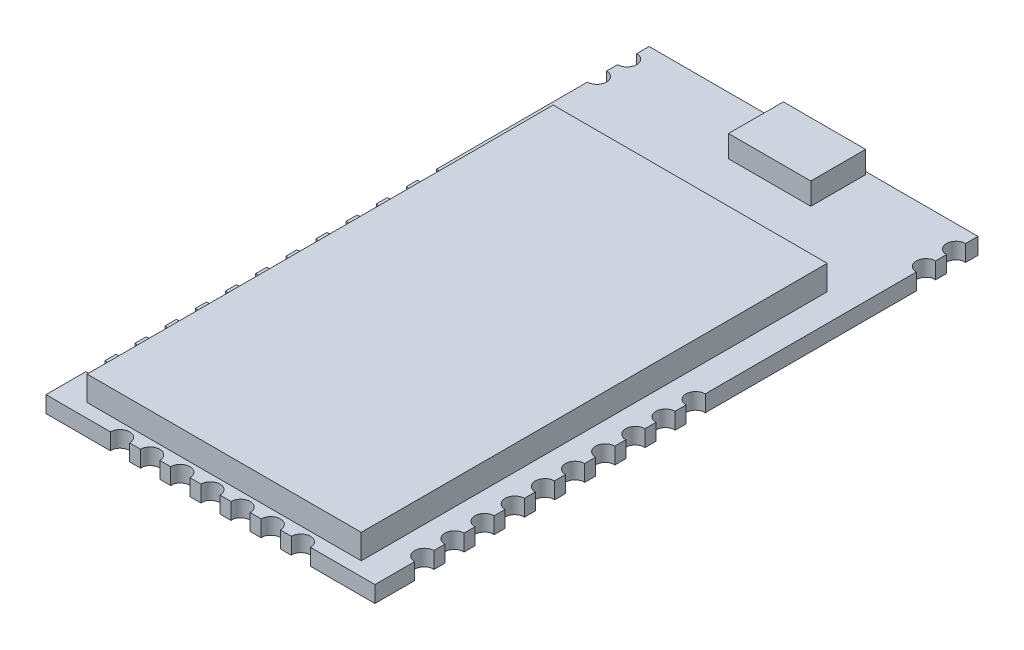
SolidWorks part; units mm, degrees
ref_plane "Front Plane" through (0, 0, 0) normal (0, 0, 1) x (1, 0, 0)
ref_plane "Top Plane" through (0, 0, 0) normal (0, 1, 0) x (1, 0, 0)
ref_plane "Right Plane" through (0, 0, 0) normal (1, 0, 0) x (0, 0, -1)
sketch "Sketch1" plane through (0, 0, 0) normal (0, 1, 0) x (1, 0, 0)
  line L0 (-6, -11) -> (-6, 11)
  line L1 (-6, 11) -> (6, 11)
  line L2 (6, 11) -> (6, -11)
  line L3 (6, -11) -> (-6, -11)
  line L4 (6, -11) -> (-6, 11) construction
  dimension "D1" = 22
  dimension "D2" = 12
extrude "Boss-Extrude1" add sketch "Sketch1" along normal blind 0.6
sketch "Sketch2" plane through (0, 0, 0) normal (0, 1, 0) x (1, 0, 0)
  line L4 (-6, -11) -> (6, -11)
  line L5 (6, -11) -> (6, 11)
  line L6 (6, 11) -> (-6, 11)
  line L7 (-6, 11) -> (-6, -11)
  line L8 (-6, -11) -> (6, -11) construction
  line L9 (6, -11) -> (6, 11) construction
  line L10 (6, 11) -> (-6, 11) construction
  line L11 (-6, 11) -> (-6, -11) construction
  circle A0 centre (-6, -9.2) radius 0.35
  circle A1 centre (-6, -8.1) radius 0.35
  circle A2 centre (-6, -7) radius 0.35
  circle A3 centre (-6, -5.9) radius 0.35
  circle A4 centre (-6, -4.8) radius 0.35
  circle A5 centre (-6, -3.7) radius 0.35
  circle A6 centre (-6, -2.6) radius 0.35
  circle A7 centre (-6, -1.5) radius 0.35
  circle A8 centre (-6, -0.4) radius 0.35
  circle A9 centre (-6, 0.7) radius 0.35
  circle A10 centre (-6, 1.8) radius 0.35
  circle A11 centre (-6, 2.9) radius 0.35
  dimension "D2" = 0.7
  dimension "D3" = 1.8
  dimension "D1" = 0
  dimension "D4" = 12
extrude "Pins left" cut sketch "Sketch2" along normal through all
sketch "Sketch3" plane through (0, 0.6, 0) normal (0, 1, 0) x (1, 0, 0)
  line L0 (-6, -11) -> (6, -11) construction
  line L1 (-6, -9.55) -> (-6, -11) construction
  circle A0 centre (-3.3, -11) radius 0.35
  circle A1 centre (-2.2, -11) radius 0.35
  circle A2 centre (-1.1, -11) radius 0.35
  circle A3 centre (0, -11) radius 0.35
  circle A4 centre (1.1, -11) radius 0.35
  circle A5 centre (2.2, -11) radius 0.35
  circle A6 centre (3.3, -11) radius 0.35
  dimension "D1" = 0.7
  dimension "D2" = 2.7
  dimension "D3" = 7
extrude "Cut-Extrude4" cut sketch "Sketch3" against normal blind 0.6
sketch "Sketch4" plane through (0, 0.6, 0) normal (0, 1, 0) x (1, 0, 0)
  line L0 (6, -11) -> (6, 11) construction
  line L1 (3.65, -11) -> (6, -11) construction
  circle A0 centre (6, -9.2) radius 0.35
  circle A1 centre (6, -8.1) radius 0.35
  circle A2 centre (6, -7) radius 0.35
  circle A3 centre (6, -5.9) radius 0.35
  circle A4 centre (6, -4.8) radius 0.35
  circle A5 centre (6, -3.7) radius 0.35
  circle A6 centre (6, -2.6) radius 0.35
  circle A7 centre (6, -1.5) radius 0.35
  circle A8 centre (6, -0.4) radius 0.35
  circle A9 centre (6, 0.7) radius 0.35
  dimension "D1" = 0.7
  dimension "D2" = 1.8
  dimension "D3" = 10
extrude "Cut-Extrude5" cut sketch "Sketch4" against normal blind 0.6
sketch "Sketch9" plane through (0, 0, 0) normal (0, -1, 0) x (1, 0, 0)
  line L0 (-6, -11) -> (-6, -3.25) construction
  line L1 (0, -11.597) -> (0, 0) construction
  circle A0 centre (-6, -9.1) radius 0.35
  circle A1 centre (-6, -10.2) radius 0.35
  circle A2 centre (6, -9.1) radius 0.35
  circle A3 centre (6, -10.2) radius 0.35
  dimension "D1" = 0.7
  dimension "D2" = 20.1
  dimension "D3" = 1.1
extrude "Cut-Extrude9" cut sketch "Sketch9" against normal blind 0.6
sketch "Sketch5" plane through (0, 0.6, 0) normal (0, 1, 0) x (1, 0, 0)
  line L0 (6, 1.05) -> (6, 8.75) construction
  line L1 (-5, 6.5) -> (5, 6.5)
  line L2 (-5, 6.5) -> (-5, -10.5)
  line L3 (-5, -10.5) -> (5, -10.5)
  line L4 (5, 6.5) -> (5, -10.5)
  line L5 (-5, 6.5) -> (5, -10.5) construction
  line L6 (-5, -10.5) -> (5, 6.5) construction
  line L7 (-6, -11) -> (-3.65, -11) construction
  line L13 (-1, 10.9) -> (2, 10.9)
  line L14 (-1, 10.9) -> (-1, 8.9)
  line L15 (-1, 8.9) -> (2, 8.9)
  line L16 (2, 10.9) -> (2, 8.9)
  line L17 (-1, 10.9) -> (2, 8.9) construction
  line L18 (-1, 8.9) -> (2, 10.9) construction
  line L19 (6, 11) -> (-6, 11) construction
  point P0 (0, -2)
  point P5 (0.5, 9.9)
  point P7 (0, -1.6618)
  point P16 (0, 0)
  point P17 (0, 0)
  point P18 (1.05, 9.1598)
  point P19 (0, 0)
  point P24 (-1, 9.9)
  dimension "D1" = 10
  dimension "D2" = 17
  dimension "D3" = 5.5
  dimension "D4" = 1.1
  dimension "D5" = 3
  dimension "D6" = 2
  dimension "D7" = 0.5
extrude "Boss-Extrude2" add sketch "Sketch5" along normal blind 0.9 contours L4 L3 L2 L1
extrude "Boss-Extrude3" add sketch "Sketch5<3>" along normal blind 0.8 contours L16 L15 L14 L13
sketch "Sketch5<3>" plane through (0, 0.6, 0) normal (0, 1, 0) x (1, 0, 0) same geometry as "Sketch5"
sketch "Sketch7" plane through (0, 0, 0) normal (0, -1, 0) x (1, 0, 0)
  line L0 (2.55, 12) -> (2.55, 10)
  line L1 (3.65, 12) -> (2.95, 12)
  line L2 (3.65, 12) -> (3.65, 10)
  line L3 (3.65, 10) -> (2.95, 10)
  line L4 (2.95, 12) -> (2.95, 10)
  line L5 (3.65, 12) -> (2.95, 10) construction
  line L6 (3.65, 10) -> (2.95, 12) construction
  line L7 (2.55, 10) -> (1.85, 10)
  line L8 (1.85, 12) -> (1.85, 10)
  line L9 (2.55, 12) -> (1.85, 12)
  line L10 (1.45, 12) -> (1.45, 10)
  line L11 (1.45, 10) -> (0.75, 10)
  line L12 (0.75, 12) -> (0.75, 10)
  line L13 (1.45, 12) -> (0.75, 12)
  line L14 (0.35, 12) -> (0.35, 10)
  line L15 (0.35, 10) -> (-0.35, 10)
  line L16 (-0.35, 12) -> (-0.35, 10)
  line L17 (0.35, 12) -> (-0.35, 12)
  line L18 (-0.75, 12) -> (-0.75, 10)
  line L19 (-0.75, 10) -> (-1.45, 10)
  line L20 (-1.45, 12) -> (-1.45, 10)
  line L21 (-0.75, 12) -> (-1.45, 12)
  line L22 (-1.85, 12) -> (-1.85, 10)
  line L23 (-1.85, 10) -> (-2.55, 10)
  line L24 (-2.55, 12) -> (-2.55, 10)
  line L25 (-1.85, 12) -> (-2.55, 12)
  line L26 (-2.95, 12) -> (-2.95, 10)
  line L27 (-2.95, 10) -> (-3.65, 10)
  line L28 (-3.65, 12) -> (-3.65, 10)
  line L29 (-2.95, 12) -> (-3.65, 12)
  arc A0 (2.95, 11) -> (3.65, 11) centre (3.3, 11) ccw construction
  point P0 (3.3, 11)
  dimension "D1" = 1
  dimension "D2" = 7
extrude "Cut-Extrude7" cut sketch "Sketch7" against normal blind 0.01
sketch "Sketch8" plane through (0, 0, 0) normal (0, -1, 0) x (1, 0, 0)
  line L0 (-5, 7.75) -> (-7, 7.75)
  line L1 (-5, 9.55) -> (-7, 9.55)
  line L2 (-5, 9.55) -> (-5, 8.85)
  line L3 (-5, 8.85) -> (-7, 8.85)
  line L4 (-7, 9.55) -> (-7, 8.85)
  line L5 (-5, 9.55) -> (-7, 8.85) construction
  line L6 (-5, 8.85) -> (-7, 9.55) construction
  line L7 (-7, 8.45) -> (-7, 7.75)
  line L8 (-5, 8.45) -> (-7, 8.45)
  line L9 (-5, 8.45) -> (-5, 7.75)
  line L10 (-5, 6.65) -> (-7, 6.65)
  line L11 (-7, 7.35) -> (-7, 6.65)
  line L12 (-5, 7.35) -> (-7, 7.35)
  line L13 (-5, 7.35) -> (-5, 6.65)
  line L14 (-5, 5.55) -> (-7, 5.55)
  line L15 (-7, 6.25) -> (-7, 5.55)
  line L16 (-5, 6.25) -> (-7, 6.25)
  line L17 (-5, 6.25) -> (-5, 5.55)
  line L18 (-5, 4.45) -> (-7, 4.45)
  line L19 (-7, 5.15) -> (-7, 4.45)
  line L20 (-5, 5.15) -> (-7, 5.15)
  line L21 (-5, 5.15) -> (-5, 4.45)
  line L22 (-5, 3.35) -> (-7, 3.35)
  line L23 (-7, 4.05) -> (-7, 3.35)
  line L24 (-5, 4.05) -> (-7, 4.05)
  line L25 (-5, 4.05) -> (-5, 3.35)
  line L26 (-5, 2.25) -> (-7, 2.25)
  line L27 (-7, 2.95) -> (-7, 2.25)
  line L28 (-5, 2.95) -> (-7, 2.95)
  line L29 (-5, 2.95) -> (-5, 2.25)
  line L30 (-5, 1.15) -> (-7, 1.15)
  line L31 (-7, 1.85) -> (-7, 1.15)
  line L32 (-5, 1.85) -> (-7, 1.85)
  line L33 (-5, 1.85) -> (-5, 1.15)
  line L34 (-5, 0.05) -> (-7, 0.05)
  line L35 (-7, 0.75) -> (-7, 0.05)
  line L36 (-5, 0.75) -> (-7, 0.75)
  line L37 (-5, 0.75) -> (-5, 0.05)
  line L38 (-5, -1.05) -> (-7, -1.05)
  line L39 (-7, -0.35) -> (-7, -1.05)
  line L40 (-5, -0.35) -> (-7, -0.35)
  line L41 (-5, -0.35) -> (-5, -1.05)
  line L42 (-5, -2.15) -> (-7, -2.15)
  line L43 (-7, -1.45) -> (-7, -2.15)
  line L44 (-5, -1.45) -> (-7, -1.45)
  line L45 (-5, -1.45) -> (-5, -2.15)
  line L46 (-5, -3.25) -> (-7, -3.25)
  line L47 (-7, -2.55) -> (-7, -3.25)
  line L48 (-5, -2.55) -> (-7, -2.55)
  line L49 (-5, -2.55) -> (-5, -3.25)
  arc A0 (-6, 8.85) -> (-6, 9.55) centre (-6, 9.2) ccw construction
  point P0 (-6, 9.2)
  dimension "D1" = 1
  dimension "D2" = 12
extrude "Cut-Extrude8" cut sketch "Sketch8" against normal blind 0.01
sketch "Sketch10" plane through (0, 0, 0) normal (0, -1, 0) x (1, 0, 0)
  line L1 (4.65, 8.85) -> (6.65, 8.85)
  line L2 (4.65, 8.85) -> (4.65, 9.55)
  line L3 (4.65, 9.55) -> (6.65, 9.55)
  line L4 (6.65, 8.85) -> (6.65, 9.55)
  line L5 (4.65, 8.85) -> (6.65, 9.55) construction
  line L6 (4.65, 9.55) -> (6.65, 8.85) construction
  line L7 (4.65, 7.75) -> (4.65, 8.45)
  line L8 (4.65, 7.75) -> (6.65, 7.75)
  line L9 (6.65, 7.75) -> (6.65, 8.45)
  line L10 (4.65, 8.45) -> (6.65, 8.45)
  line L11 (4.65, 6.65) -> (4.65, 7.35)
  line L12 (4.65, 6.65) -> (6.65, 6.65)
  line L13 (6.65, 6.65) -> (6.65, 7.35)
  line L14 (4.65, 7.35) -> (6.65, 7.35)
  line L15 (4.65, 5.55) -> (4.65, 6.25)
  line L16 (4.65, 5.55) -> (6.65, 5.55)
  line L17 (6.65, 5.55) -> (6.65, 6.25)
  line L18 (4.65, 6.25) -> (6.65, 6.25)
  line L19 (4.65, 4.45) -> (4.65, 5.15)
  line L20 (4.65, 4.45) -> (6.65, 4.45)
  line L21 (6.65, 4.45) -> (6.65, 5.15)
  line L22 (4.65, 5.15) -> (6.65, 5.15)
  line L23 (4.65, 3.35) -> (4.65, 4.05)
  line L24 (4.65, 3.35) -> (6.65, 3.35)
  line L25 (6.65, 3.35) -> (6.65, 4.05)
  line L26 (4.65, 4.05) -> (6.65, 4.05)
  line L27 (4.65, 2.25) -> (4.65, 2.95)
  line L28 (4.65, 2.25) -> (6.65, 2.25)
  line L29 (6.65, 2.25) -> (6.65, 2.95)
  line L30 (4.65, 2.95) -> (6.65, 2.95)
  line L31 (4.65, 1.15) -> (4.65, 1.85)
  line L32 (4.65, 1.15) -> (6.65, 1.15)
  line L33 (6.65, 1.15) -> (6.65, 1.85)
  line L34 (4.65, 1.85) -> (6.65, 1.85)
  line L35 (4.65, 0.05) -> (4.65, 0.75)
  line L36 (4.65, 0.05) -> (6.65, 0.05)
  line L37 (6.65, 0.05) -> (6.65, 0.75)
  line L38 (4.65, 0.75) -> (6.65, 0.75)
  line L39 (4.65, -1.05) -> (4.65, -0.35)
  line L40 (4.65, -1.05) -> (6.65, -1.05)
  line L41 (6.65, -1.05) -> (6.65, -0.35)
  line L42 (4.65, -0.35) -> (6.65, -0.35)
  arc A0 (6, 9.55) -> (6, 8.85) centre (6, 9.2) ccw construction
  point P0 (5.65, 9.2)
  dimension "D1" = 1
  dimension "D2" = 0.7
  dimension "D3" = 10
extrude "Cut-Extrude10" cut sketch "Sketch10" against normal blind 0.01
sketch "Sketch11" plane through (0, 0, 0) normal (0, -1, 0) x (1, 0, 0)
  line L0 (0, 0) -> (0, -14.827) construction
  line L1 (4.65, -10.55) -> (6.65, -10.55)
  line L2 (4.65, -10.55) -> (4.65, -9.85)
  line L3 (4.65, -9.85) -> (6.65, -9.85)
  line L4 (6.65, -10.55) -> (6.65, -9.85)
  line L5 (4.65, -10.55) -> (6.65, -9.85) construction
  line L6 (4.65, -9.85) -> (6.65, -10.55) construction
  line L7 (4.65, -9.45) -> (6.65, -9.45)
  line L8 (4.65, -9.45) -> (4.65, -8.75)
  line L9 (4.65, -8.75) -> (6.65, -8.75)
  line L10 (6.65, -9.45) -> (6.65, -8.75)
  line L11 (4.65, -9.45) -> (6.65, -8.75) construction
  line L12 (4.65, -8.75) -> (6.65, -9.45) construction
  line L13 (-4.65, -9.85) -> (-6.65, -9.85)
  line L14 (-6.65, -10.55) -> (-6.65, -9.85)
  line L15 (-4.65, -10.55) -> (-6.65, -10.55)
  line L16 (-4.65, -10.55) -> (-4.65, -9.85)
  line L17 (-4.65, -8.75) -> (-6.65, -8.75)
  line L18 (-6.65, -9.45) -> (-6.65, -8.75)
  line L19 (-4.65, -9.45) -> (-6.65, -9.45)
  line L20 (-4.65, -9.45) -> (-4.65, -8.75)
  arc A0 (6, -9.85) -> (6, -10.55) centre (6, -10.2) ccw construction
  arc A1 (6, -8.75) -> (6, -9.45) centre (6, -9.1) ccw construction
  point P0 (5.65, -10.2)
  point P8 (5.65, -9.1)
  dimension "D1" = 0.7
  dimension "D2" = 1
  dimension "D3" = 1
  dimension "D4" = 0.7
extrude "Cut-Extrude11" cut sketch "Sketch11" against normal blind 0.01
